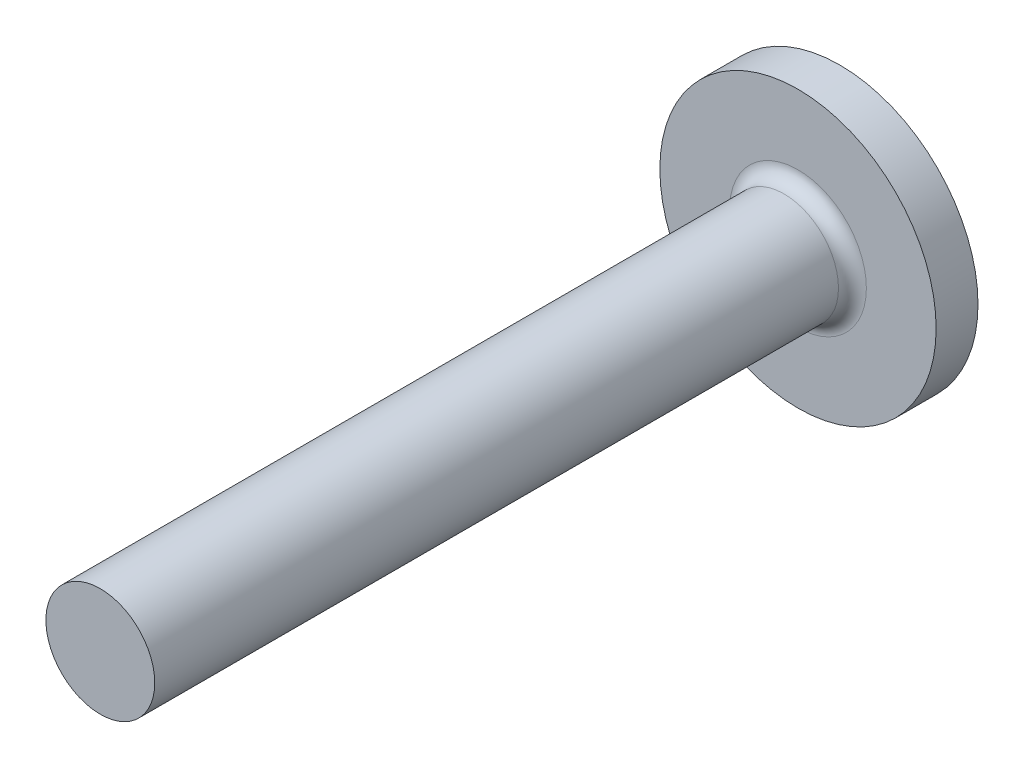
SolidWorks part; units mm, degrees
ref_plane "Front Plane" through (0, 0, 0) normal (0, 0, 1) x (1, 0, 0)
ref_plane "Top Plane" through (0, 0, 0) normal (0, 1, 0) x (1, 0, 0)
ref_plane "Right Plane" through (0, 0, 0) normal (1, 0, 0) x (0, 0, -1)
sketch "Sketch1" plane through (0, 0, 0) normal (0, 0, 1) x (1, 0, 0)
  circle A0 centre (0, 0) radius 3.9
  circle A1 centre (0, 0) radius 9.9
  dimension "D1" = 7.8
  dimension "D2" = 6
extrude "Boss-Extrude1" add sketch "Sketch1" along normal blind 50 contours A0 region at (0, 0, 0)
extrude "Boss-Extrude2" add sketch "Sketch1<3>" against normal blind 3 contours A1 A0 | A0 region at (0, 0, 0) region at (-9.62, 0, 0)
sketch "Sketch1<3>" plane through (0, 0, 0) normal (0, 0, 1) x (1, 0, 0) same geometry as "Sketch1"
fillet "Fillet1" radius 1 1 edges at (3.9, 0, 0)
